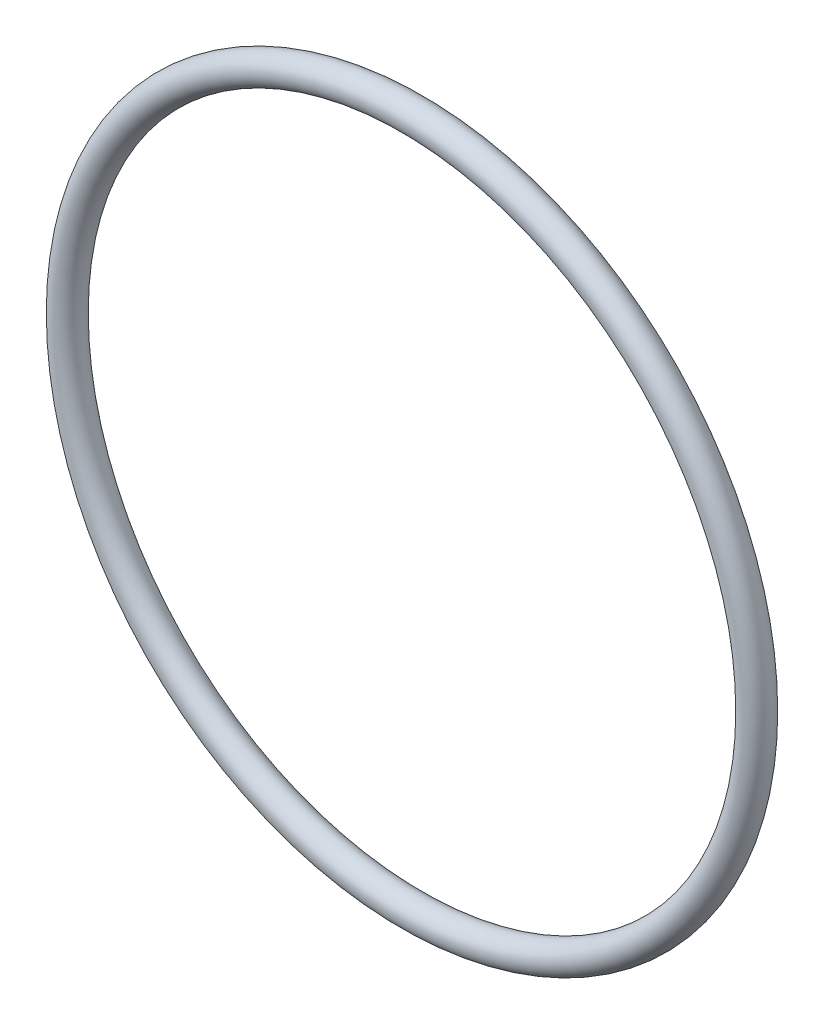
SolidWorks part; units mm, degrees
ref_plane "Front" through (0, 0, 0) normal (0, 0, 1) x (1, 0, 0)
ref_plane "Top" through (0, 0, 0) normal (0, 1, 0) x (1, 0, 0)
ref_plane "Right" through (0, 0, 0) normal (1, 0, 0) x (0, 0, -1)
sketch "Sketch1" plane through (0, 0, 0) normal (0, 0, 1) x (1, 0, 0)
  circle A0 centre (0, 0) radius 20
  dimension "d1" = 40
sketch "Sketch2" plane through (0, 0, 0) normal (0, 1, 0) x (1, 0, 0)
  circle A0 centre (-20.9, 0) radius 0.9
  point P2 (-20, 0)
  dimension "d2" = 1.8
sweep "Sweep1" add profiles "Sketch2" path "Sketch1"
ref_axis "Axis1" through (0, 0, -4.6197) along (0, 0, 1)
